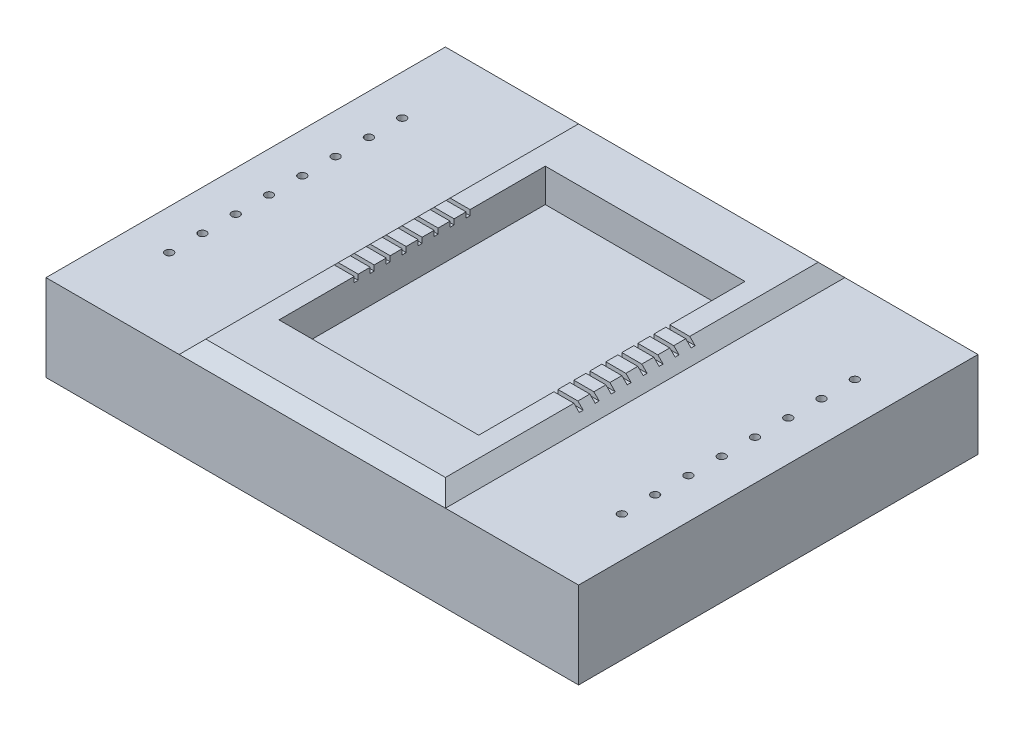
SolidWorks part; units mm, degrees
material "Plain Carbon Steel"
ref_plane "Front Plane" through (0, 0, 0) normal (0, 0, 1) x (1, 0, 0)
ref_plane "Top Plane" through (0, 0, 0) normal (0, 1, 0) x (1, 0, 0)
ref_plane "Right Plane" through (0, 0, 0) normal (1, 0, 0) x (0, 0, -1)
sketch "Sketch1" plane through (0, 0, 0) normal (0, 1, 0) x (1, 0, 0)
  line L1 (-50.8, 38.1) -> (50.8, 38.1)
  line L2 (-50.8, 38.1) -> (-50.8, -38.1)
  line L3 (-50.8, -38.1) -> (50.8, -38.1)
  line L4 (50.8, 38.1) -> (50.8, -38.1)
  line L5 (-50.8, 38.1) -> (50.8, -38.1) construction
  line L6 (-50.8, -38.1) -> (50.8, 38.1) construction
  point P0 (0, 0)
  dimension "D1" = 76.2
  dimension "D2" = 101.6
extrude "Boss-Extrude1" add sketch "Sketch1" along normal blind 19.05
sketch "Sketch2" plane through (0, 19.05, 0) normal (0, 1, 0) x (1, 0, 0)
  line L1 (-19.05, 25.4) -> (19.05, 25.4)
  line L2 (-19.05, 25.4) -> (-19.05, -25.4)
  line L3 (-19.05, -25.4) -> (19.05, -25.4)
  line L4 (19.05, 25.4) -> (19.05, -25.4)
  line L5 (-19.05, 25.4) -> (19.05, -25.4) construction
  line L6 (-19.05, -25.4) -> (19.05, 25.4) construction
  point P0 (0, 0)
  dimension "D1" = 50.8
  dimension "D2" = 38.1
extrude "Cut-Extrude1" cut sketch "Sketch2" against normal blind 6.35
sketch "Sketch3" plane through (0, 0, 38.1) normal (0, 0, 1) x (1, 0, 0)
  line L1 (-50.8, 19.05) -> (-25.4, 19.05)
  line L2 (-50.8, 19.05) -> (-50.8, 16.51)
  line L3 (-50.8, 16.51) -> (-25.4, 16.51)
  line L4 (-25.4, 19.05) -> (-25.4, 16.51)
  line L5 (50.8, 19.05) -> (25.4, 19.05)
  line L6 (50.8, 19.05) -> (50.8, 16.51)
  line L7 (50.8, 16.51) -> (25.4, 16.51)
  line L8 (25.4, 19.05) -> (25.4, 16.51)
  line L10 (-50.8, 0) -> (50.8, 0) construction
  point P10 (0, 0)
  dimension "D1" = 2.54
  dimension "D2" = 25.4
  dimension "D3" = 25.4
extrude "Cut-Extrude2" cut sketch "Sketch3" against normal through all
chamfer "Chamfer1" distance 2.54 angle 45 4 edges at (25.4, 19.05, 0) (-25.4, 19.05, 0) (0, 19.05, -38.1) (0, 19.05, 38.1)
sketch "Sketch4" plane through (0, 16.51, 0) normal (0, 1, 0) x (1, 0, 0)
  line L0 (-43.18, -22.225) -> (-43.18, 22.225) construction
  line L1 (-50.8, 38.1) -> (-50.8, -38.1) construction
  circle A0 centre (-43.18, 22.225) radius 0.762
  point P2 (-43.18, 0)
  dimension "D2" = 1.524
  dimension "D1" = 44.45
  dimension "D3" = 7.62
extrude "Cut-Extrude3" cut sketch "Sketch4" against normal blind 6.35 contours A0
pattern_linear "LPattern1" count 8 spacing 6.35 along (0, 0, 1) of "Cut-Extrude3"
mirror "Mirror1" about plane through (0, 0, 0) normal (1, 0, 0) of "LPattern1"
sketch "Sketch6" plane through (-50.8, 0, 0) normal (-1, 0, 0) x (0, 0, 1)
  line L0 (-10.668, 19.05) -> (10.668, 19.05) construction
  line L1 (-35.56, 19.05) -> (35.56, 19.05) construction
  line L3 (-11.049, 19.05) -> (-10.287, 19.05)
  line L4 (-11.049, 19.05) -> (-11.049, 18.034)
  line L5 (-11.049, 18.034) -> (-10.287, 18.034)
  line L6 (-10.287, 19.05) -> (-10.287, 18.034)
  point P4 (0, 19.05)
  point P10 (-10.668, 19.05)
  dimension "D1" = 0.762
  dimension "D2" = 1.016
  dimension "D3" = 21.336
extrude "Cut-Extrude8" cut sketch "Sketch6" against normal through all contours L4 L5 L6 L3
pattern_linear "LPattern2" count 8 spacing 3.048 along (0, 0, 1) of "Cut-Extrude8"
equation "\"n\"=11"
